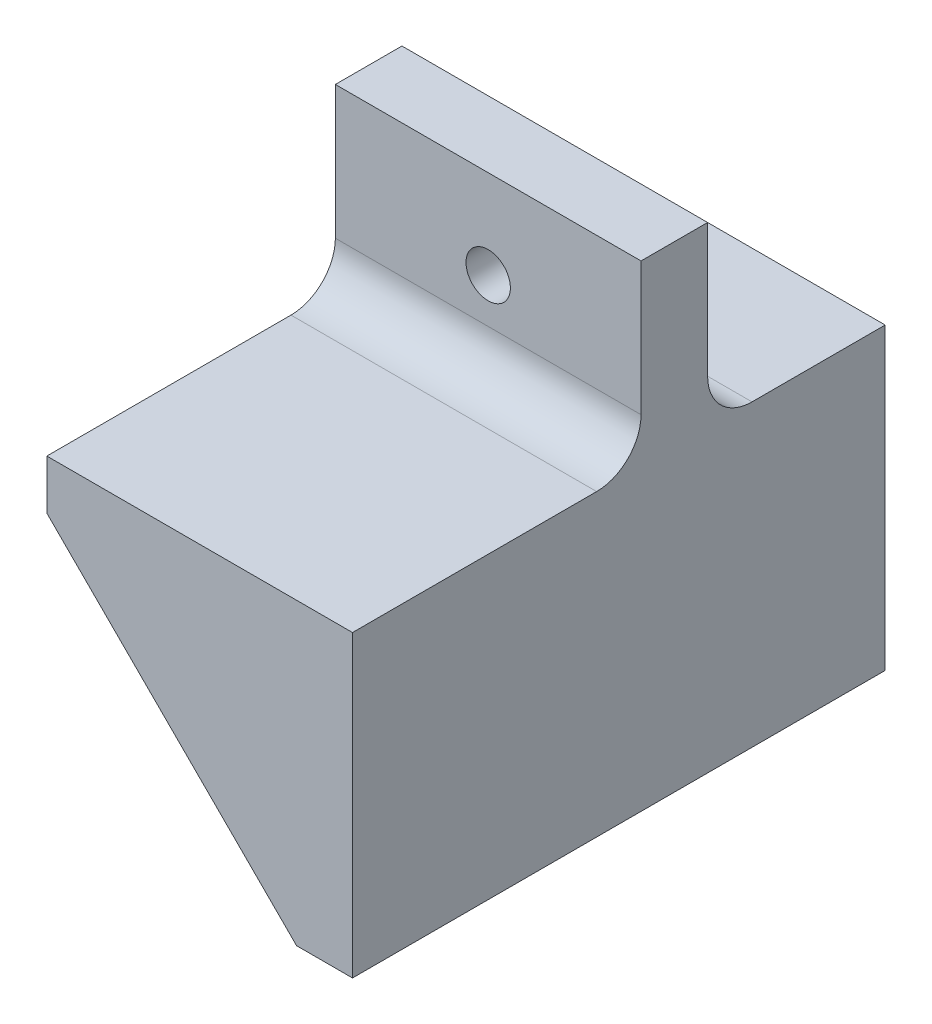
SolidWorks part; units mm, degrees
ref_plane "Front Plane" through (0, 0, 0) normal (0, 0, 1) x (1, 0, 0)
ref_plane "Top Plane" through (0, 0, 0) normal (0, 1, 0) x (1, 0, 0)
ref_plane "Right Plane" through (0, 0, 0) normal (1, 0, 0) x (0, 0, -1)
sketch "Sketch1" plane through (0, 0, 0) normal (0, 0, 1) x (1, 0, 0)
  line L0 (30.841, 29.7939) -> (-19.959, -21.0061)
  line L3 (-19.959, -21.0061) -> (30.841, -21.0061)
  line L4 (30.841, 29.7939) -> (30.841, -21.0061)
  dimension "D1" = 50.8
extrude "Boss-Extrude1" add sketch "Sketch1" along normal blind 76.2
sketch "Sketch2" plane through (0, 0, 0) normal (0, 1, 0) x (1, 0, 0)
  line L0 (-19.959, -76.2) -> (-19.959, 0) construction
  line L1 (-19.959, -4.572) -> (26.269, -4.572)
  line L2 (-19.959, -4.572) -> (-19.959, -71.628)
  line L3 (-19.959, -71.628) -> (26.269, -71.628)
  line L4 (26.269, -4.572) -> (26.269, -71.628)
  line L5 (30.841, 0) -> (-19.959, 0) construction
  line L6 (30.841, -76.2) -> (-19.959, -76.2) construction
  line L7 (30.841, -76.2) -> (30.841, 0) construction
  dimension "D1" = 4.572
  dimension "D2" = 4.572
  dimension "D3" = 4.572
extrude "Cut-Extrude1" cut sketch "Sketch2" along normal blind 32 and the other way blind 11.079
chamfer "Chamfer2" distance 8 angle 90 1 edges at (30.841, 29.7939, 38.1) first distance on face at (30.841, 4.3939, 38.1)
chamfer "Chamfer3" distance 10 angle 45 1 edges at (-19.959, -21.0061, 38.1) first distance on face at (3.9228, 2.8757, 38.1)
sketch "Sketch3" plane through (0, -11.079, 0) normal (0, 1, 0) x (1, 0, 0)
  line L2 (30.841, -25.4) -> (-12.8879, 0) construction
  line L3 (30.841, 0) -> (-12.8879, 0) construction
  line L4 (30.841, 0) -> (30.841, -25.4) construction
  line L5 (30.841, -25.4) -> (-12.8879, -25.4) construction
  line L6 (-12.8879, -76.2) -> (30.841, -76.2)
  line L7 (-12.8879, 0) -> (-12.8879, -76.2)
  line L8 (30.841, 0) -> (-12.8879, 0)
  line L9 (30.841, -76.2) -> (30.841, 0)
  line L10 (-12.8879, -76.2) -> (30.841, -76.2) construction
  line L11 (-12.8879, 0) -> (-12.8879, -76.2) construction
  line L12 (30.841, 0) -> (-12.8879, 0) construction
  line L13 (30.841, -76.2) -> (30.841, 0) construction
  line L14 (-12.8879, 0) -> (-12.8879, -25.4) construction
  circle A0 centre (8.9766, -12.7) radius 3.175
  dimension "D1" = 0
  dimension "D2" = 25.4
extrude "Cut-Extrude2" cut sketch "Sketch3" against normal through all contours A0
sketch "Sketch8" plane through (0, -21.0061, 0) normal (0, -1, 0) x (1, 0, 0)
  line L0 (30.841, 76.2) -> (30.841, 0) construction
  line L1 (-12.8879, 0) -> (30.841, 0) construction
  line L2 (-12.8879, 0) -> (-12.8879, 25.4) construction
  line L3 (-12.8879, 25.4) -> (30.841, 25.4) construction
  line L4 (30.841, 0) -> (30.841, 25.4) construction
  line L6 (-12.8879, 25.4) -> (30.841, 25.4)
  line L7 (-12.8879, 25.4) -> (-12.8879, 34.925)
  line L8 (-12.8879, 34.925) -> (30.841, 34.925)
  line L9 (30.841, 25.4) -> (30.841, 34.925)
  dimension "D1" = 25.4
  dimension "D2" = 9.525
extrude "Boss-Extrude3" add sketch "Sketch8" along normal blind 25.4
sketch "Sketch9" plane through (0, 0, 34.925) normal (0, 0, 1) x (1, 0, 0)
  circle A0 centre (8.9766, -33.7061) radius 3.175
extrude "Cut-Extrude3" cut sketch "Sketch9" against normal through all
fillet "Fillet2" radius 6.35 2 edges at (8.9766, -21.0061, 25.4) (8.9766, -21.0061, 34.925)
mirror "Mirror1" about plane through (0, 0, 0) normal (0, 1, 0) of bodies 106
delete or keep bodies "Body-Delete/Keep 1" type delete bodies bodies 106
